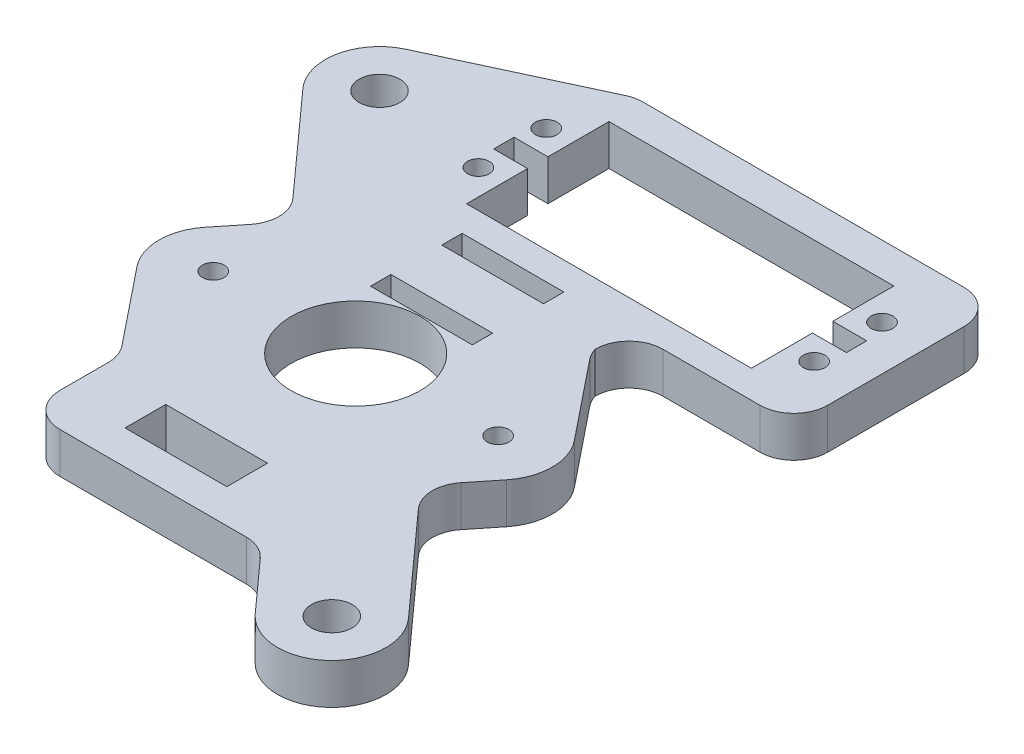
SolidWorks part; units mm, degrees
material "MDF"
ref_plane "Plano frontal" through (0, 0, 0) normal (0, 0, 1) x (1, 0, 0)
ref_plane "Plano superior" through (0, 0, 0) normal (0, 1, 0) x (1, 0, 0)
ref_plane "Plano direito" through (0, 0, 0) normal (1, 0, 0) x (0, 0, -1)
ref_plane "Plano1" through (0, -6, 0) normal (0, -1, 0) x (1, 0, 0)
sketch "Esboço1" plane through (0, -6, 0) normal (0, -1, 0) x (1, 0, 0)
  line L0 (30.7936, -136.5537) -> (52.8946, -146.8291)
  line L1 (55.0026, -147.2952) -> (102.3526, -147.2952)
  line L2 (107.3526, -142.2952) -> (107.3526, -122.2)
  line L3 (102.3526, -117.2) -> (88.05, -117.2)
  line L4 (83.05, -112.2) -> (83.05, -88.8837)
  line L5 (84.3343, -85.538) -> (103.6789, -64.0537)
  line L6 (91.7885, -53.3476) -> (85.0372, -60.8457)
  line L7 (81.3215, -62.5) -> (53.85, -62.5)
  line L8 (48.85, -67.5) -> (48.85, -99.1163)
  line L9 (47.5657, -102.462) -> (28.2211, -123.9463)
  line L10 (73.45, -114.2) -> (73.45, -117.2)
  line L11 (73.45, -117.2) -> (58.45, -117.2)
  line L12 (58.45, -117.2) -> (58.45, -114.2)
  line L13 (58.45, -114.2) -> (73.45, -114.2)
  line L14 (58.45, -108) -> (58.45, -105)
  line L15 (58.45, -105) -> (73.45, -105)
  line L16 (73.45, -105) -> (73.45, -108)
  line L17 (73.45, -108) -> (58.45, -108)
  line L18 (58.45, -67.5) -> (73.45, -67.5)
  line L19 (73.45, -67.5) -> (73.45, -73.5)
  line L20 (73.45, -73.5) -> (58.45, -73.5)
  line L21 (58.45, -73.5) -> (58.45, -67.5)
  line L22 (55.0026, -142.2952) -> (55.0026, -121.2952)
  line L23 (55.0026, -121.2952) -> (97.0026, -121.2952)
  line L24 (97.0026, -121.2952) -> (97.0026, -142.2952)
  line L25 (97.0026, -142.2952) -> (55.0026, -142.2952)
  line L26 (34.1663, -129.2994) -> (97.7337, -58.7006) construction
  line L27 (44.95, -94) -> (86.95, -94) construction
  line L28 (44.3524, -106.0308) -> (38.7129, -99.0099)
  line L29 (38.7129, -88.9901) -> (48.85, -76.3698)
  line L30 (83.05, -111.6302) -> (93.1871, -99.0099)
  line L31 (93.1871, -88.9901) -> (87.5476, -81.9692)
  arc A0 (52.8946, -146.8291) -> (55.0026, -147.2952) centre (55.0026, -142.2952) ccw
  arc A1 (102.3526, -147.2952) -> (107.3526, -142.2952) centre (102.3526, -142.2952) ccw
  arc A2 (107.3526, -122.2) -> (102.3526, -117.2) centre (102.3526, -122.2) ccw
  arc A3 (88.05, -117.2) -> (83.05, -112.2) centre (88.05, -112.2) cw
  arc A4 (83.05, -88.8837) -> (84.3343, -85.538) centre (88.05, -88.8837) cw
  arc A5 (103.6789, -64.0537) -> (91.7885, -53.3476) centre (97.7337, -58.7006) ccw
  arc A6 (85.0372, -60.8457) -> (81.3215, -62.5) centre (81.3215, -57.5) cw
  arc A7 (53.85, -62.5) -> (48.85, -67.5) centre (53.85, -67.5) ccw
  arc A8 (48.85, -99.1163) -> (47.5657, -102.462) centre (43.85, -99.1163) cw
  arc A9 (28.2211, -123.9463) -> (30.7936, -136.5537) centre (34.1663, -129.2994) ccw
  circle A10 centre (65.95, -94) radius 9.5
  circle A11 centre (44.95, -94) radius 1.6
  circle A12 centre (86.95, -94) radius 1.6
  arc A13 (38.7129, -99.0099) -> (38.7129, -88.9901) centre (44.95, -94) cw
  arc A14 (93.1871, -99.0099) -> (93.1871, -88.9901) centre (86.95, -94) ccw
  circle A15 centre (100.7526, -126.7952) radius 1.6
  circle A16 centre (100.7526, -136.7952) radius 1.6
  circle A17 centre (51.2526, -126.7952) radius 1.6
  circle A18 centre (51.2526, -136.7952) radius 1.6
  circle A19 centre (34.1663, -129.2994) radius 3
  circle A20 centre (97.7337, -58.7006) radius 3
  point P37 (65.95, -105)
  point P41 (65.95, -94)
  point P68 (36.95, -94)
  point P74 (94.95, -94)
  dimension "D16" = 3.2
  dimension "D20" = 6
  dimension "D25" = 5
  dimension "D27" = 19
  dimension "D1" = 42
  dimension "D2" = 21
  dimension "D3" = 10
  dimension "D4" = 49.5
  dimension "D5" = 95
  dimension "D6" = 3
  dimension "D7" = 15
  dimension "D8" = 34.2
  dimension "D9" = 6
  dimension "D10" = 14.6974
  dimension "D11" = 32.7952
  dimension "D12" = 40.7
  dimension "D13" = 6.2
  dimension "D14" = 5
  dimension "D15" = 5
  dimension "D17" = 5.5
  dimension "D18" = 3.75
  dimension "D19" = 48
  dimension "D21" = 8
  dimension "D22" = 9.6
  dimension "D23" = 6.6
  dimension "D24" = 4.0952
  dimension "D26" = 11
  dimension "D28" = 42
  dimension "D29" = 8
  dimension "D30" = 30
  dimension "D31" = 30
extrude "Ressalto-extrusão1" add sketch "Esboço1" against normal blind 6 contours L9 A9 L0 A0 L1 A1 L2 A2 L3 A3 L4 A4 L5 A5 L6 A6 L7 A7 L8 A8 A19 A17 A15 L12 L13 L10 L11 L16 L17 L14 L15 L20 L21 L18 L19 L24 L25 L22 L23 | L30 A14 L31 L5 A4 L4 A12 | A13 L28 L9 A8 L8 L29 A11 region at (68.7945, -6, -103.5655) region at (44.0199, -6, -92.593) region at (87.8801, -6, -95.407)
fillet "Filete1" radius 5 4 edges at (83.05, -3, -111.6302) (87.5476, -3, -81.9692) (48.85, -3, -76.3698) (44.3524, -3, -106.0308)
sketch "Esboço2" plane through (0, -6, 0) normal (0, -1, 0) x (1, 0, 0)
  line L1 (58.45, -105) -> (73.45, -105)
  line L2 (58.45, -105) -> (58.45, -103.7)
  line L3 (58.45, -103.7) -> (73.45, -103.7)
  line L4 (73.45, -105) -> (73.45, -103.7)
  line L9 (55.0026, -142.2952) -> (55.0026, -121.2952) construction
  line L10 (50.0026, -133.2952) -> (55.0026, -133.2952)
  line L11 (50.0026, -133.2952) -> (50.0026, -130.2952)
  line L12 (50.0026, -130.2952) -> (55.0026, -130.2952)
  line L13 (55.0026, -133.2952) -> (55.0026, -130.2952)
  line L14 (52.5026, -130.2952) -> (52.5026, -133.2952) construction
  line L15 (50.0026, -131.7952) -> (55.0026, -131.7952) construction
  line L16 (76.0026, -121.2952) -> (76.0026, -142.2952) construction
  line L17 (55.0026, -121.2952) -> (97.0026, -121.2952) construction
  line L18 (97.0026, -142.2952) -> (55.0026, -142.2952) construction
  line L19 (102.0026, -130.2952) -> (97.0026, -130.2952)
  line L20 (97.0026, -133.2952) -> (97.0026, -130.2952)
  line L21 (102.0026, -133.2952) -> (97.0026, -133.2952)
  line L22 (102.0026, -133.2952) -> (102.0026, -130.2952)
  point P5 (52.5026, -131.7952)
  point P23 (0, 0)
  point P24 (76.0026, -131.7952)
  dimension "D1" = 1.3
  dimension "D2" = 3
  dimension "D3" = 5
extrude "Corte-extrusão1" cut sketch "Esboço2" against normal through all
sketch "Esboço3" plane through (0, -6, 0) normal (0, -1, 0) x (1, 0, 0)
  line L0 (73.45, -103.7) -> (73.45, -108) construction
  line L1 (58.45, -108) -> (73.45, -108)
  line L2 (58.45, -108) -> (58.45, -106.7)
  line L3 (58.45, -106.7) -> (73.45, -106.7)
  line L4 (73.45, -108) -> (73.45, -106.7)
  dimension "D1" = 1.3
extrude "Ressalto-extrusão2" add sketch "Esboço3" against normal blind 6
